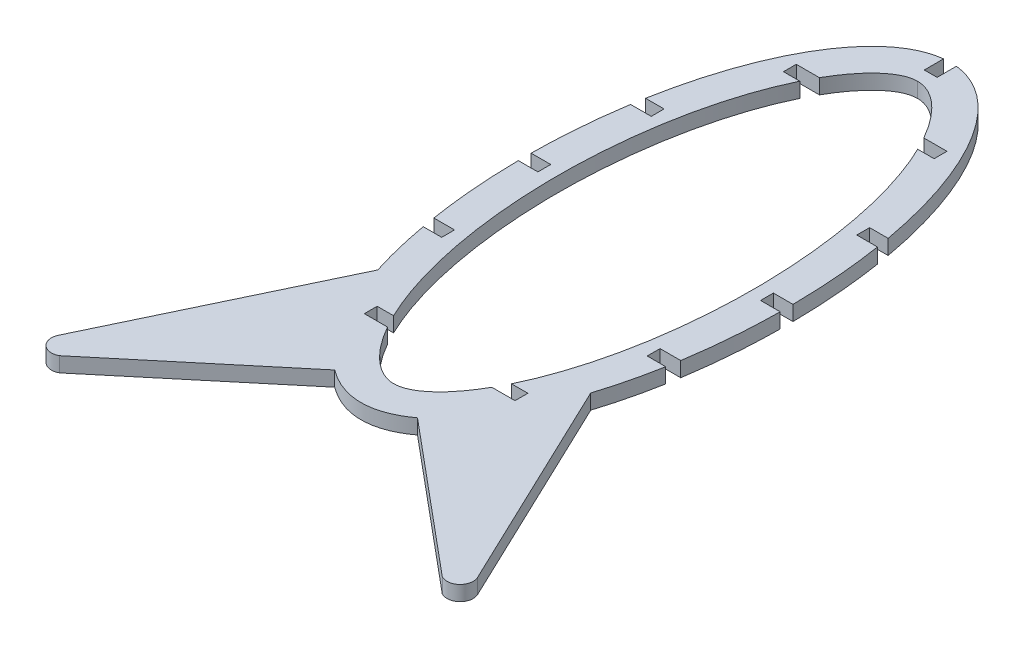
SolidWorks part; units mm, degrees
ref_plane "Front Plane" through (0, 0, 0) normal (0, 0, 1) x (1, 0, 0)
ref_plane "Top Plane" through (0, 0, 0) normal (0, 1, 0) x (1, 0, 0)
ref_plane "Right Plane" through (0, 0, 0) normal (1, 0, 0) x (0, 0, -1)
sketch "Sketch1" plane through (0, 0, 0) normal (0, 1, 0) x (1, 0, 0)
  line L2 (25.4, 0) -> (-45.1447, 0) construction
  line L3 (21.59, 0) -> (30.3971, 0) construction
  line L4 (21.59, 1.2446) -> (25.394, 1.2446)
  line L5 (21.59, 1.2446) -> (21.59, -1.2446)
  line L6 (21.59, -1.2446) -> (25.394, -1.2446)
  line L8 (37.0979, -78.485) -> (8.0291, -54.2196)
  line L9 (40.6569, -75.1899) -> (20.6588, -33.2492)
  line L10 (23.7402, 20.32) -> (29.3413, 20.32) construction
  line L11 (19.9302, 21.5646) -> (23.5224, 21.5646)
  line L12 (19.9302, 21.5646) -> (19.9302, 19.0754)
  line L13 (19.9302, 19.0754) -> (23.9434, 19.0754)
  line L19 (14.0482, 40.64) -> (-23.5224, 40.64) construction
  line L20 (0, 57.15) -> (0, 41.8846) construction
  line L21 (-37.0979, -78.485) -> (-8.0291, -54.2196)
  line L22 (-14.6132, -41.8846) -> (-10.1242, -41.8846)
  line L23 (-14.6132, -41.8846) -> (-14.6132, -39.3954)
  line L24 (-14.6132, -39.3954) -> (-11.4313, -39.3954)
  line L25 (19.9302, -21.5646) -> (23.5224, -21.5646)
  line L26 (19.9302, -21.5646) -> (19.9302, -19.0754)
  line L27 (19.9302, -19.0754) -> (23.9434, -19.0754)
  line L28 (-40.6569, -75.1899) -> (-20.6588, -33.2492)
  line L29 (14.6132, 41.8846) -> (10.1242, 41.8846)
  line L30 (14.6132, 41.8846) -> (14.6132, 39.3954)
  line L31 (14.6132, 39.3954) -> (11.4313, 39.3954)
  line L32 (-19.9302, -21.5646) -> (-23.5224, -21.5646)
  line L33 (-19.9302, -21.5646) -> (-19.9302, -19.0754)
  line L34 (-19.9302, -19.0754) -> (-23.9434, -19.0754)
  line L35 (-21.59, 1.2446) -> (-21.59, -1.2446)
  line L36 (-21.59, 1.2446) -> (-25.394, 1.2446)
  line L37 (-21.59, -1.2446) -> (-25.394, -1.2446)
  line L38 (-19.9302, 21.5646) -> (-23.5224, 21.5646)
  line L39 (-19.9302, 21.5646) -> (-19.9302, 19.0754)
  line L40 (-19.9302, 19.0754) -> (-23.9434, 19.0754)
  line L41 (14.6132, -39.3954) -> (11.4313, -39.3954)
  line L42 (-14.6132, 41.8846) -> (-10.1242, 41.8846)
  line L43 (-14.6132, 41.8846) -> (-14.6132, 39.3954)
  line L44 (-14.6132, 39.3954) -> (-11.4313, 39.3954)
  line L46 (0, 39.3954) -> (0, -57.15) construction
  line L47 (14.6132, -41.8846) -> (14.6132, -39.3954)
  line L48 (14.6132, -41.8846) -> (10.1242, -41.8846)
  line L49 (0, 57.15) -> (0, 53.34) construction
  line L51 (-1.2446, 57.0814) -> (-1.2446, 53.34)
  line L52 (-1.2446, 53.34) -> (1.2446, 53.34)
  line L53 (1.2446, 57.0814) -> (1.2446, 53.34)
  arc A0 (37.0979, -78.485) -> (40.6569, -75.1899) centre (38.3642, -76.2831) ccw
  arc A1 (-37.0979, -78.485) -> (-40.6569, -75.1899) centre (-38.3642, -76.2831) cw
  ellipse E0 centre (0, 0) end of major axis (0, 57.15) minor radius 25.4 (-23.9434, 19.0754) -> (-25.394, 1.2446) ccw
  ellipse E1 centre (0, 0) end of major axis (0, 57.15) minor radius 25.4 (-25.394, -1.2446) -> (-23.9434, -19.0754) ccw
  ellipse E2 centre (0, 0) end of major axis (0, 57.15) minor radius 25.4 (-23.5224, -21.5646) -> (-20.6588, -33.2492) ccw
  ellipse E3 centre (0, 0) end of major axis (0, 57.15) minor radius 25.4 (23.9434, -19.0754) -> (25.394, -1.2446) ccw
  ellipse E4 centre (0, 0) end of major axis (0, 57.15) minor radius 25.4 (25.394, 1.2446) -> (23.9434, 19.0754) ccw
  ellipse E5 centre (0, 0) end of major axis (0, 57.15) minor radius 25.4 (23.5224, 21.5646) -> (1.2446, 57.0814) ccw
  ellipse E6 centre (0, 0) end of major axis (0, 57.15) minor radius 25.4 (-1.2446, 57.0814) -> (-23.5224, 21.5646) ccw
  ellipse E7 centre (0, 0) end of major axis (0, 57.15) minor radius 25.4 (-8.0291, -54.2196) -> (8.0291, -54.2196) ccw
  ellipse E8 centre (0, 0) end of major axis (0, 57.15) minor radius 25.4 (20.6588, -33.2492) -> (23.5224, -21.5646) ccw
  spline S0 degree 3 poles (10.1242, 41.8846) (9.6963, 42.6376) (8.1175, 45.2063) (5.3181, 48.5143) (2.7404, 50.1903) (1.0874, 50.7223) (0.3742, 50.8) (0, 50.8) knots -0.663564 -0.663564 -0.663564 -0.663564 -0.589049 -0.392699 -0.19635 -0.098175 0 0 0 0
  spline S1 degree 3 poles (0, -50.8) (0.3742, -50.8) (1.0874, -50.7223) (2.7404, -50.1903) (5.3181, -48.5143) (8.1175, -45.2063) (9.6963, -42.6376) (10.1242, -41.8846) knots -3.141593 -3.141593 -3.141593 -3.141593 -3.043418 -2.945243 -2.748894 -2.552544 -2.478028 -2.478028 -2.478028 -2.478028
  spline S2 degree 3 poles (0, -50.8) (-0.3742, -50.8) (-1.0874, -50.7223) (-2.7404, -50.1903) (-5.3181, -48.5143) (-8.1175, -45.2063) (-9.6963, -42.6376) (-10.1242, -41.8846) knots -3.141593 -3.141593 -3.141593 -3.141593 -3.043418 -2.945243 -2.748894 -2.552544 -2.478028 -2.478028 -2.478028 -2.478028
  spline S3 degree 3 poles (-10.1242, 41.8846) (-9.6963, 42.6376) (-8.1175, 45.2063) (-5.3181, 48.5143) (-2.7404, 50.1903) (-1.0874, 50.7223) (-0.3742, 50.8) (0, 50.8) knots -0.663564 -0.663564 -0.663564 -0.663564 -0.589049 -0.392699 -0.19635 -0.098175 0 0 0 0
  spline S4 degree 3 poles (-11.4313, -39.3954) (-11.6771, -38.8896) (-12.9878, -36.0709) (-15.1482, -30.1662) (-18.0998, -17.7755) (-19.6835, 0) (-18.0998, 17.7755) (-15.1482, 30.1662) (-12.9878, 36.0709) (-11.6771, 38.8896) (-11.4313, 39.3954) knots -2.400746 -2.400746 -2.400746 -2.400746 -2.356194 -2.159845 -1.963495 -1.570796 -1.178097 -0.981748 -0.785398 -0.740847 -0.740847 -0.740847 -0.740847
  spline S5 degree 3 poles (11.4313, -39.3954) (11.6771, -38.8896) (12.9878, -36.0709) (15.1482, -30.1662) (18.0998, -17.7755) (19.6835, 0) (18.0998, 17.7755) (15.1482, 30.1662) (12.9878, 36.0709) (11.6771, 38.8896) (11.4313, 39.3954) knots -2.400746 -2.400746 -2.400746 -2.400746 -2.356194 -2.159845 -1.963495 -1.570796 -1.178097 -0.981748 -0.785398 -0.740847 -0.740847 -0.740847 -0.740847
  point P25 (19.9302, 20.32)
  point P35 (44.1664, -82.55)
  dimension "D5" = 2.54
  dimension "D1" = 114.3
  dimension "D2" = 25.4
  dimension "D3" = 25.4
  dimension "D4" = 2.4892
  dimension "D6" = 3.81
  dimension "D7" = 2.4892
  dimension "D9" = 3.81
  dimension "D10" = 2.4892
  dimension "D11" = 0
  dimension "D12" = 3.81
extrude "Boss-Extrude2" add sketch "Sketch1" along normal blind 2.8956
equation "\"thickness\" = 0.114"
